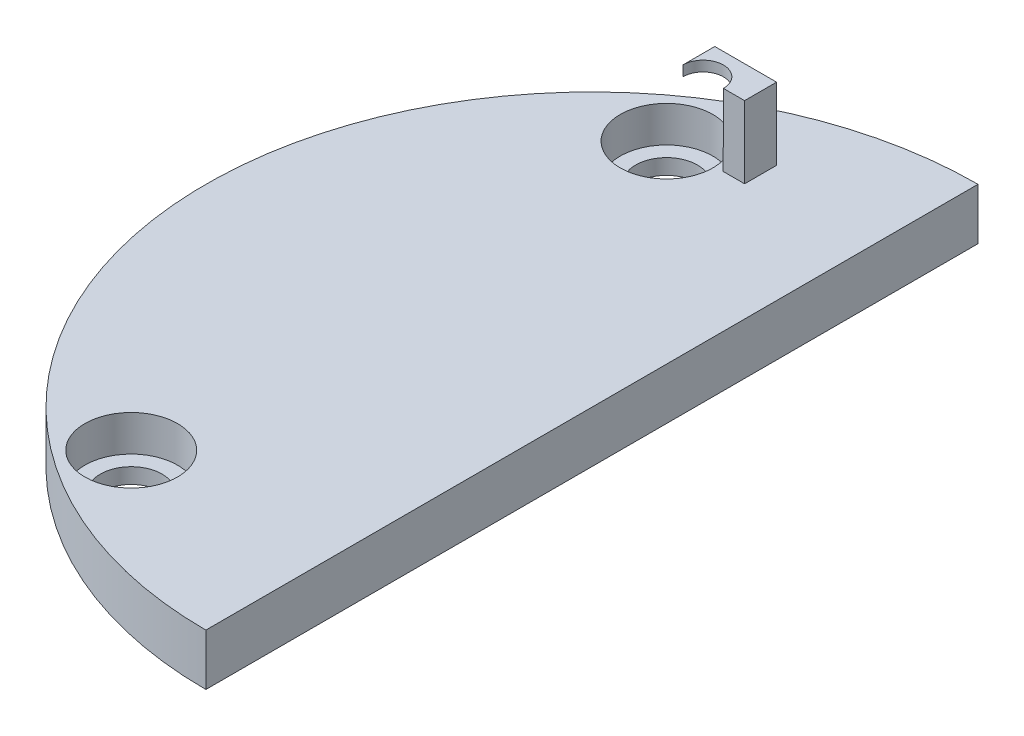
SolidWorks part; units mm, degrees
ref_plane "Ebene vorne" through (0, 0, 0) normal (0, 0, 1) x (1, 0, 0)
ref_plane "Ebene oben" through (0, 0, 0) normal (0, 1, 0) x (1, 0, 0)
ref_plane "Ebene rechts" through (0, 0, 0) normal (1, 0, 0) x (0, 0, -1)
sketch "Skizze1" plane through (0, 0, 0) normal (0, 1, 0) x (1, 0, 0)
  line L0 (0, 0) -> (0, -75)
  line L1 (0, -37.5) -> (-48.465, -37.5) construction
  arc A1 (0, -75) -> (0, 0) centre (0, -37.5) cw
  dimension "D1" = 75
extrude "Aufsatz-Linear austragen1" add sketch "Skizze1" along normal blind 5
sketch "Skizze11" plane through (0, 5, 0) normal (0, 1, 0) x (1, 0, 0)
  line L0 (0, -37.5) -> (-37.5, -37.5) construction
  line L1 (0, -75) -> (0, 0) construction
  line L2 (-18.75, -37.5) -> (-18.75, -1.2821) construction
  line L3 (-18.75, -1.2821) -> (-18.75, -74.2151) construction
  arc A0 (0, 0) -> (0, -75) centre (0, -37.5) ccw construction
  circle A1 centre (-18.75, -11.5) radius 4.5
  circle A2 centre (-18.75, -63.5) radius 4.5
  dimension "D1" = 52
  dimension "D2" = 9
extrude "Schnitt-Linear austragen1" cut sketch "Skizze11" against normal blind 3.5
sketch "Skizze12" plane through (0, 1.5, 0) normal (0, 1, 0) x (1, 0, 0)
  circle A0 centre (-18.75, -63.5) radius 3
  circle A1 centre (-18.75, -11.5) radius 3
extrude "Schnitt-Linear austragen2" cut sketch "Skizze12" against normal blind 1.5
sketch "Skizze13" plane through (0, 5, 0) normal (0, 1, 0) x (1, 0, 0)
  line L0 (-13.4591, -11.2984) -> (-11.3733, -11.2984)
  line L1 (-11.3733, -8.1916) -> (-13.4591, -8.1916)
  line L2 (-13.4591, -8.1916) -> (-13.4591, -11.2984)
  line L3 (-11.3733, -8.1916) -> (-11.3733, -11.2984)
extrude "Aufsatz-Linear austragen2" add sketch "Skizze13" along normal blind 6
sketch "Skizze14" plane through (0, 11, 0) normal (0, 1, 0) x (1, 0, 0)
  line L0 (-11.3733, -8.1916) -> (-11.3733, -11.2984)
  line L1 (-11.3733, -11.2984) -> (-17.3733, -11.2984)
  line L2 (-17.3733, -11.2984) -> (-17.3733, -8.1916)
  line L3 (-17.3733, -8.1916) -> (-11.3733, -8.1916)
extrude "Aufsatz-Linear austragen3" add sketch "Skizze14" along normal blind 1
sketch "Skizze16" plane through (0, 12, 0) normal (0, 1, 0) x (1, 0, 0)
  line L0 (-17.3733, -11.2984) -> (-13.43, -11.2984)
  line L1 (-17.3733, -11.2984) -> (-11.3733, -11.2984) construction
  arc A0 (-13.43, -11.2984) -> (-17.3733, -11.2984) centre (-15.4017, -11.2984) ccw
extrude "Schnitt-Linear austragen3" cut sketch "Skizze16" against normal blind 5
